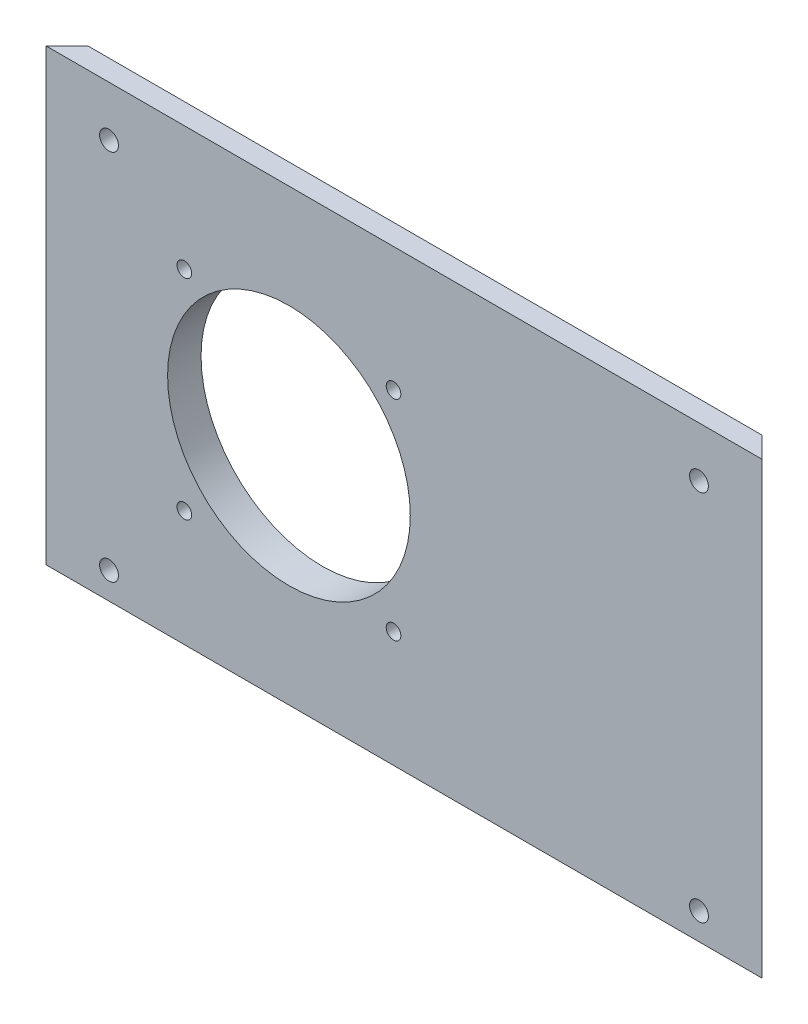
SolidWorks part; units mm, degrees
ref_plane "Front Plane" through (0, 0, 0) normal (0, 0, 1) x (1, 0, 0)
ref_plane "Top Plane" through (0, 0, 0) normal (0, 1, 0) x (1, 0, 0)
ref_plane "Right Plane" through (0, 0, 0) normal (1, 0, 0) x (0, 0, -1)
sketch "Sketch1" plane through (0, 0, 0) normal (0, 0, 1) x (1, 0, 0)
  line L0 (85.5, 110) -> (85.5, -37.3998) construction
  line L1 (0, 0) -> (171, 0)
  line L2 (0, 0) -> (0, 110)
  line L3 (0, 110) -> (171, 110)
  line L4 (171, 0) -> (171, 110)
  line L5 (0, 55) -> (171, 55) construction
  circle A0 centre (15, 9) radius 2.25
  circle A1 centre (156, 9) radius 2.25
  circle A4 centre (15, 98) radius 2.25
  circle A5 centre (156, 98) radius 2.25
  dimension "D3" = 15
  dimension "D5" = 4.5
  dimension "D1" = 110
  dimension "D2" = 171
  dimension "D4" = 9
  dimension "D6" = 2
  dimension "D7" = 12
extrude "Boss-Extrude1" add sketch "Sketch1" against normal blind 5
sketch "Sketch2" plane through (0, 0, -5) normal (0, 0, -1) x (-1, 0, 0)
  line L0 (0, 0) -> (-171, 0) construction
  line L1 (0, 0) -> (-171, 0) construction
  line L2 (0, 5) -> (-171, 5)
  line L3 (-171, 5) -> (-171, 110)
  line L4 (-171, 110) -> (0, 110)
  line L5 (0, 110) -> (0, 5)
  circle A1 centre (-15, 9) radius 2.25 construction
  circle A2 centre (-156, 9) radius 2.25 construction
  circle A5 centre (-15, 9) radius 2.25
  circle A6 centre (-156, 9) radius 2.25
  circle A8 centre (-15, 98) radius 2.25 construction
  circle A9 centre (-156, 98) radius 2.25 construction
  circle A10 centre (-15, 98) radius 2.25
  circle A11 centre (-156, 98) radius 2.25
  dimension "D1" = 5
extrude "Boss-Extrude2" add sketch "Sketch2" along normal blind 3
chamfer "Chamfer1" distance 8 angle 45 3 edges at (171, 57.5, -8) (0, 57.5, -8) (85.5, 110, -8)
chamfer "Chamfer3" distance 3 angle 45 1 edges at (85.5, 110, -8)
sketch "Sketch3" plane through (85.5, 0, -85.5) normal (0.7071, 0, -0.7071) x (-0.7071, 0, -0.7071)
  line L0 (-120.9153, 0) -> (-120.9153, 2.6)
  line L1 (-120.9153, 0) -> (-120.9153, 110) construction
  line L2 (-120.9153, 2.6) -> (-113.8442, 2.6)
  line L4 (-113.8442, 2.6) -> (-113.8442, 0)
  line L5 (-113.8442, 0) -> (-120.9153, 0)
  line L6 (-109.6016, 5) -> (-113.8442, 5) construction
  dimension "D1" = 2.4
extrude "Cut-Extrude1" cut sketch "Sketch3" along direction (1, 0, 0) on the side against the normal through all
sketch "Sketch4" plane through (0, 0, 0) normal (0, 0, 1) x (1, 0, 0)
  line L0 (171, 110) -> (0, 110) construction
  line L1 (93, 66) -> (141, 66) construction
  line L2 (93, 66) -> (93, 95) construction
  line L3 (93, 95) -> (141, 95) construction
  line L4 (141, 66) -> (141, 95) construction
  line L5 (171, 2.6) -> (171, 110) construction
  line L6 (111, 99.75) -> (111, 61.25) construction
  line L7 (93, 80.5) -> (141, 80.5) construction
  line L8 (29, 56.3) -> (28, 56.3) construction
  line L9 (28, 56.3) -> (28, 85.3) construction
  line L10 (28, 85.3) -> (58, 85.3) construction
  line L11 (28, 80.3) -> (33, 80.3) construction
  line L12 (33, 80.3) -> (33, 85.3) construction
  circle A0 centre (58, 56.3) radius 29
  circle A1 centre (33, 80.3) radius 1.75
  circle A2 centre (83, 80.3) radius 1.75
  circle A3 centre (83, 30.3) radius 1.75
  circle A4 centre (33, 30.3) radius 1.75
  circle A5 centre (111, 99.75) radius 1.75 construction
  circle A6 centre (111, 61.25) radius 1.75 construction
  point P28 (111, 80.5)
  dimension "D5" = 58
  dimension "D6" = 53.7
  dimension "D8" = 5
  dimension "D11" = 3.5
  dimension "D1" = 29
  dimension "D2" = 48
  dimension "D3" = 15
  dimension "D4" = 30
  dimension "D7" = 35
  dimension "D9" = 5
  dimension "D10" = 1
  dimension "D14" = 38.5
  dimension "D15" = 0
  dimension "D12" = 2
  dimension "D13" = 2
extrude "Cut-Extrude2" cut sketch "Sketch4" against normal through all
